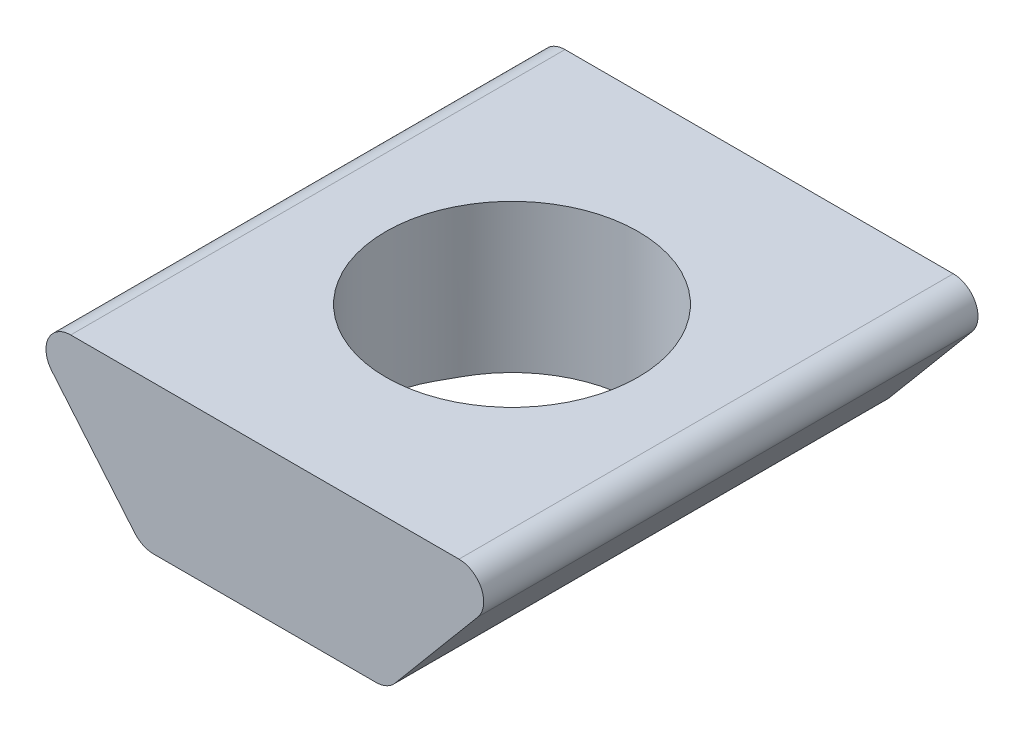
SolidWorks part; units mm, degrees
ref_plane "Front Plane" through (0, 0, 0) normal (0, 0, 1) x (1, 0, 0)
ref_plane "Top Plane" through (0, 0, 0) normal (0, 1, 0) x (1, 0, 0)
ref_plane "Right Plane" through (0, 0, 0) normal (1, 0, 0) x (0, 0, -1)
sketch "Sketch2" plane through (0, 0, 0) normal (0, 0, 1) x (1, 0, 0)
  line L0 (-5, 0) -> (5, 0)
  line L1 (5, 0) -> (2.4827, -3)
  line L2 (2.4827, -3) -> (-2.4827, -3)
  line L3 (-2.4827, -3) -> (-5, 0)
  point P4 (0, 0)
  dimension "D1" = 10
  dimension "D2" = 3
  dimension "D3" = 50
extrude "Boss-Extrude1" add sketch "Sketch2" along normal blind 10
sketch "Sketch3" plane through (0, 0, 0) normal (0, 1, 0) x (1, 0, 0)
  line L0 (-5, 0) -> (5, -10) construction
  point P4 (0, -5)
hole_wizard "Tap Drill for 1/4-20 Tap1" positions "Sketch3" profile "Sketch4" hole size "1/4-20" standard "ANSI Inch" end condition through all
sketch "Sketch4" plane through (0, 0, 5) normal (1, 0, 0) x (0, 0, 1)
  line L0 (0, 0) -> (0, 3)
  line L1 (0, 3) -> (2.5527, 3)
  line L2 (2.5527, 3) -> (2.5527, 0)
  line L5 (2.5527, 0) -> (0, 0)
  line L11 (0, -6.35) -> (0, 107.95) construction
  dimension "Thru Hole Dia." = 5.1054
  dimension "Thru Hole Depth" = 3
fillet "Fillet1" radius 0.5 4 edges at (2.4827, -3, 7.7968) (-2.4827, -3, 7.7968) (5, 0, 5) (-5, 0, 5)
